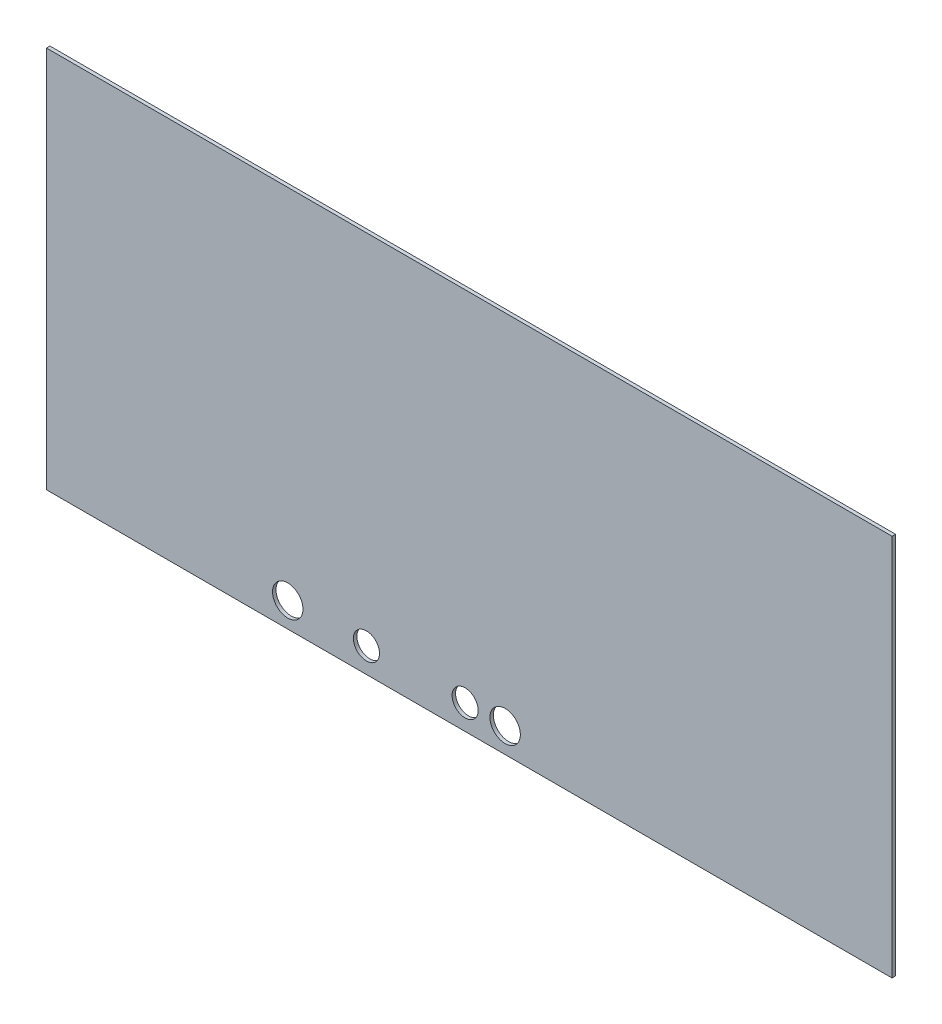
SolidWorks part; units mm, degrees
ref_plane "Ön Düzlem" through (0, 0, 0) normal (0, 0, 1) x (1, 0, 0)
ref_plane "Üst Düzlem" through (0, 0, 0) normal (0, 1, 0) x (1, 0, 0)
ref_plane "Sağ Düzlem" through (0, 0, 0) normal (1, 0, 0) x (0, 0, -1)
sketch "Çizim1" plane through (0, 0, 0) normal (0, 0, 1) x (1, 0, 0)
  line L1 (0, 0) -> (1955, 0) construction
  line L2 (0, 0) -> (0, -887) construction
  line L3 (0, -887) -> (1955, -887) construction
  line L4 (1955, 0) -> (1955, -887) construction
  line L8 (1941.0266, -2868.1757) -> (1453.696, -2800.553) construction
  line L9 (555, -830) -> (1055, -830) construction
  line L10 (0, -887) -> (1945, -887)
  line L11 (1945, -887) -> (1945, -7)
  line L12 (1945, -7) -> (0, -7)
  line L13 (0, -7) -> (0, -887)
  circle A0 centre (555, -830) radius 35
  circle A1 centre (736, -830) radius 30
  circle A2 centre (963, -830) radius 30
  circle A3 centre (1055, -830) radius 35
  dimension "D3" = 70
  dimension "D5" = 60
  dimension "D7" = 60
  dimension "D8" = 70
  dimension "D1" = 887
  dimension "D2" = 1955
  dimension "D4" = 555
  dimension "D6" = 736
  dimension "D9" = 963
  dimension "D10" = 1055
  dimension "D11" = 57
  dimension "D12" = 500
  dimension "D13" = 181
  dimension "D14" = 227
  dimension "D15" = 92
  dimension "D16" = 880
  dimension "D17" = 1945
base flange "Taban-Flanş1" sketch "Çizim1" thickness 8 reverse thickness direction no parameters "D1"=6
sketch "Büküm-Çizgileri1" [suppressed] plane through (0, 0, 0) normal (0, 1, 0) x (1, 0, 0)
sketch "Sınırlandırma-Kutusu1" [suppressed] plane through (0, 0, 0) normal (0, 1, 0) x (1, 0, 0)
sheet metal parameters "Sac-Levha1" thickness 8 parameters "D1"=6
flat pattern "Düz-Çoğaltma1" [suppressed]
sketch "Büküm-Çizgileri2" plane through (0, 0, 0) normal (0, 1, 0) x (1, 0, 0)
sketch3d "Sınırlandırma-Kutusu2" [suppressed]
  line L0 (0, -887, 0) -> (1945, -887, 0) construction
  line L1 (0, -7, 0) -> (1945, -7, 0) construction
  line L2 (0, -887, 0) -> (0, -7, 0) construction
  line L3 (1945, -887, 0) -> (1945, -7, 0) construction
